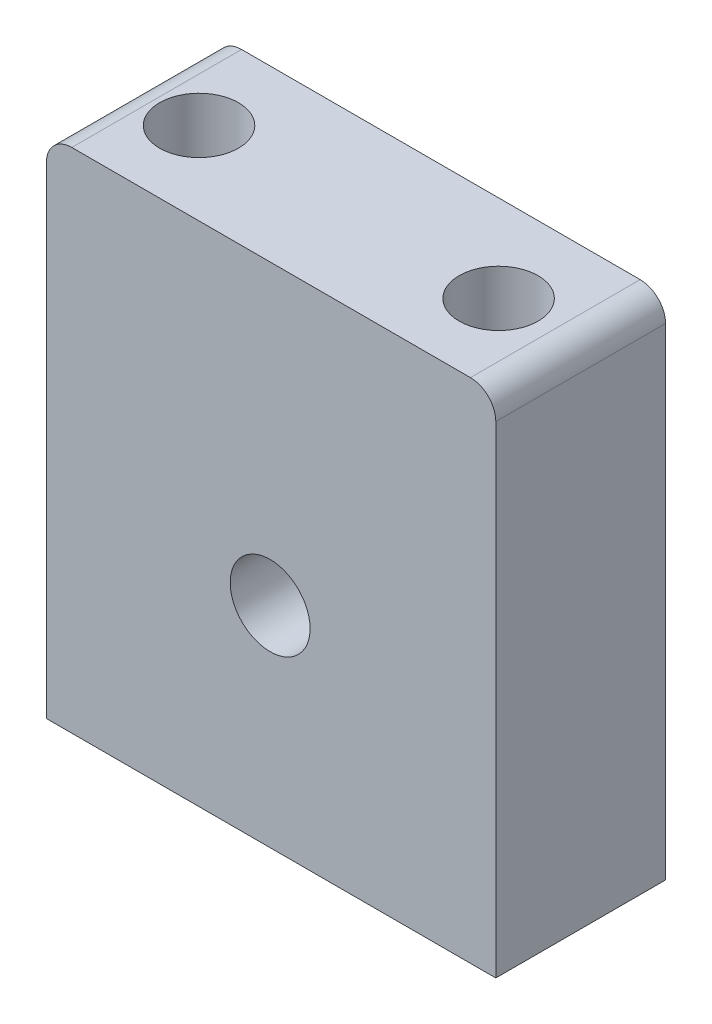
SolidWorks part; units mm, degrees
ref_plane "Front Plane" through (0, 0, 0) normal (0, 0, 1) x (1, 0, 0)
ref_plane "Top Plane" through (0, 0, 0) normal (0, 1, 0) x (1, 0, 0)
ref_plane "Right Plane" through (0, 0, 0) normal (1, 0, 0) x (0, 0, -1)
sketch "Sketch1" plane through (0, 0, 0) normal (0, 0, 1) x (1, 0, 0)
  line L1 (0, 0) -> (45, 0)
  line L2 (0, 0) -> (0, 50.8)
  line L3 (0, 50.8) -> (45, 50.8)
  line L4 (45, 0) -> (45, 50.8)
  circle A0 centre (22.4, 21) radius 4
  dimension "D3" = 8
  dimension "D1" = 45
  dimension "D2" = 50.8
  dimension "D4" = 21
  dimension "D5" = 22.4
extrude "Boss-Extrude1" add sketch "Sketch1" along normal blind 17
sketch "Sketch2" plane through (0, 50.8, 0) normal (0, 1, 0) x (1, 0, 0)
  line L0 (0, -17) -> (0, 0) construction
  circle A0 centre (7, -8.7186) radius 3.95
  circle A1 centre (37, -8.7186) radius 3.95
  dimension "D1" = 7.9
  dimension "D3" = 7.9
  dimension "D2" = 7
  dimension "D4" = 30
extrude "Cut-Extrude1" cut sketch "Sketch2" against normal blind 17
fillet "Fillet1" radius 2.54 2 edges at (0, 50.8, 8.5) (45, 50.8, 8.5)
